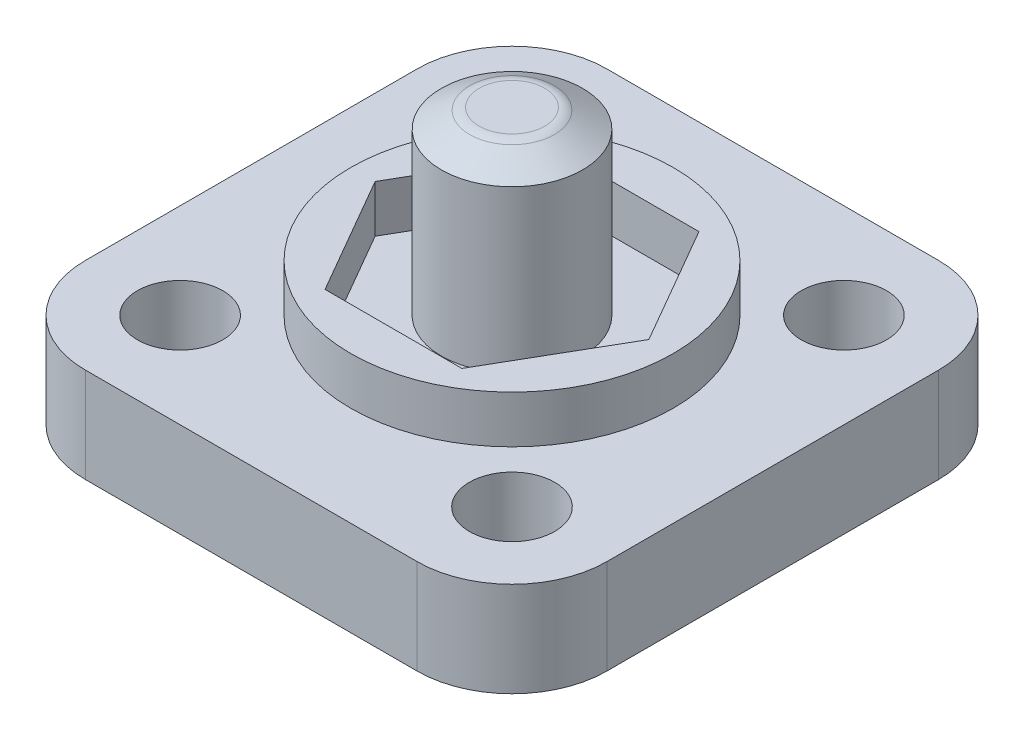
SolidWorks part; units mm, degrees
ref_plane "Front Plane" through (0, 0, 0) normal (0, 0, 1) x (1, 0, 0)
ref_plane "Top Plane" through (0, 0, 0) normal (0, 1, 0) x (1, 0, 0)
ref_plane "Right Plane" through (0, 0, 0) normal (1, 0, 0) x (0, 0, -1)
sketch "Sketch1" plane through (0, 0, 0) normal (0, 0, 1) x (1, 0, 0)
  line L0 (0, 9.5) -> (0, -9.5) construction
  line L1 (0, 9.5) -> (3.4622, 9.5)
  line L2 (4.4653, 9.2303) -> (7.45, 7.5)
  line L3 (7.45, 7.5) -> (7.45, -4.5)
  line L4 (7.45, -9.5) -> (0, -9.5)
  line L5 (0, 9.5) -> (0, -9.5)
  line L6 (7.45, -4.5) -> (17, -4.5)
  line L7 (17, -4.5) -> (17, -9.5)
  line L8 (17, -9.5) -> (7.45, -9.5)
  arc A0 (3.4622, 9.5) -> (4.4653, 9.2303) centre (3.4622, 7.5) cw
  point P4 (0, 0)
  point P10 (4, 9.5)
  dimension "D5" = 2
  dimension "D1" = 17
  dimension "D2" = 2
  dimension "D3" = 14.9
  dimension "D4" = 4
  dimension "D6" = 17
  dimension "D7" = 5
revolve "Revolve1" add sketch "Sketch1" angle 360 about L0
sketch "Sketch2" plane through (0, -9.5, 0) normal (0, -1, 0) x (1, 0, 0)
  line L0 (27.5, 27.5) -> (-27.5, -27.5) construction
  line L1 (17.5, 27.5) -> (-17.5, 27.5)
  line L2 (27.5, 17.5) -> (27.5, -17.5)
  line L3 (17.5, -27.5) -> (-17.5, -27.5)
  line L4 (-27.5, 17.5) -> (-27.5, -17.5)
  arc A0 (-17.5, 27.5) -> (-27.5, 17.5) centre (-17.5, 17.5) ccw
  arc A1 (-17.5, -27.5) -> (-27.5, -17.5) centre (-17.5, -17.5) cw
  arc A2 (27.5, -17.5) -> (17.5, -27.5) centre (17.5, -17.5) cw
  arc A3 (17.5, 27.5) -> (27.5, 17.5) centre (17.5, 17.5) cw
  dimension "D2" = 10
  dimension "D1" = 55
extrude "Boss-Extrude1" add sketch "Sketch2" along normal blind 10
sketch "Sketch3" plane through (0, -9.5, 0) normal (0, 1, 0) x (1, 0, 0)
  circle A0 centre (-17.5, 17.5) radius 4.5
  dimension "D1" = 9
extrude "Cut-Extrude1" cut sketch "Sketch3" against normal through all
mirror "Mirror1" about plane through (0, 0, 0) normal (0, 0, 1) of "Cut-Extrude1" second plane through (0, 0, 0) second plane normal (1, 0, 0)
sketch "Sketch4" plane through (0, -4.5, 0) normal (0, 1, 0) x (1, 0, 0)
  line L1 (14.4338, 0) -> (7.2169, 12.5)
  line L2 (7.2169, 12.5) -> (-7.2169, 12.5)
  line L3 (-7.2169, 12.5) -> (-14.4338, 0)
  line L4 (-14.4338, 0) -> (-7.2169, -12.5)
  line L5 (-7.2169, -12.5) -> (7.2169, -12.5)
  line L6 (7.2169, -12.5) -> (14.4338, 0)
  circle A0 centre (0, 0) radius 12.5 construction
  circle A1 centre (0, 0) radius 7.45 construction
  circle A2 centre (0, 0) radius 7.45
  point P1 (0, 0)
  dimension "D1" = 25
extrude "Cut-Extrude3" cut sketch "Sketch4" against normal blind 5
